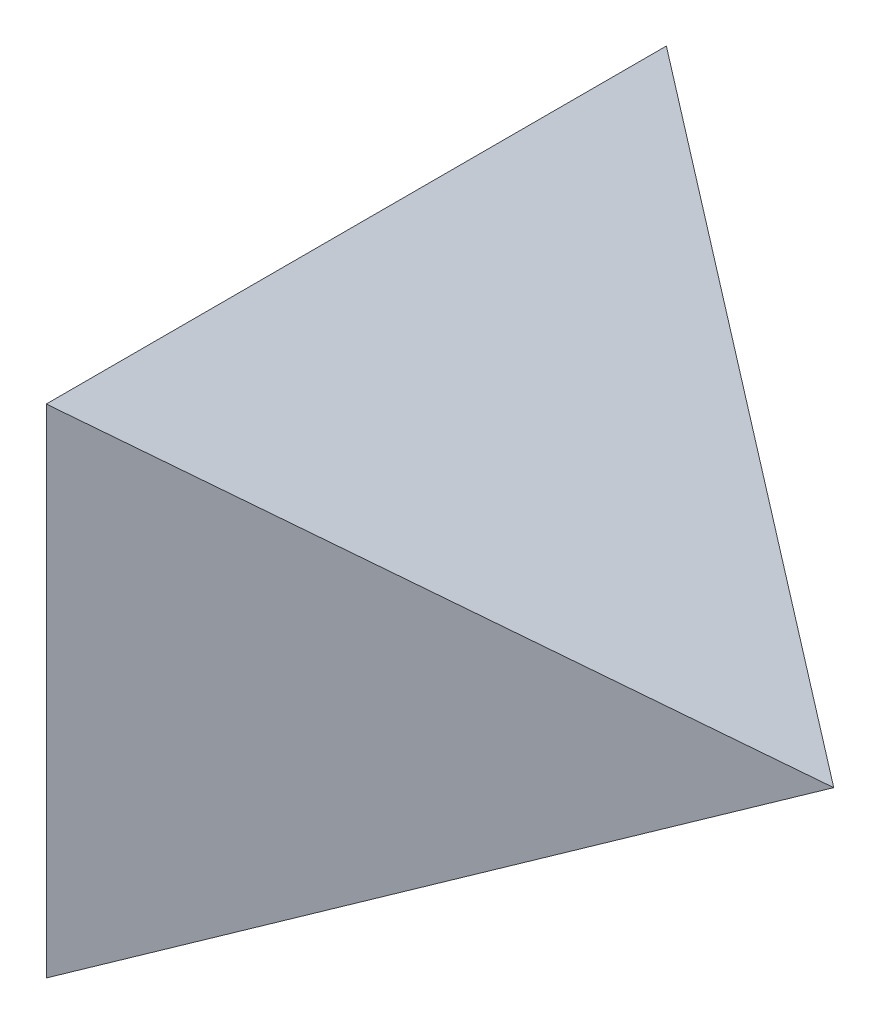
SolidWorks part; units mm, degrees
ref_plane "Front Plane" through (0, 0, 0) normal (0, 0, 1) x (1, 0, 0)
ref_plane "Top Plane" through (0, 0, 0) normal (0, 1, 0) x (1, 0, 0)
ref_plane "Right Plane" through (0, 0, 0) normal (1, 0, 0) x (0, 0, -1)
sketch "Sketch1" plane through (0, 0, 0) normal (0, 0, 1) x (1, 0, 0)
  line L0 (0, 0) -> (-3000, 1561.7012)
  line L1 (0, 0) -> (-3000, -1561.7012)
  line L2 (0, 0) -> (-3000, 0) construction
  line L3 (-3000, 1561.7012) -> (-3000, -1561.7012)
  dimension "D1" = 55
  dimension "D2" = 3000
extrude "Boss-Extrude1" add sketch "Sketch1" along normal blind 3000 and the other way blind 3000
sketch "Sketch2" plane through (0, 0, 0) normal (0, 1, 0) x (1, 0, 0)
  line L0 (0, 0) -> (-3000, 1948.2228)
  line L1 (-3000, 3000) -> (-3000, -3000) construction
  line L2 (-3000, 1948.2228) -> (-3000, -1948.2228)
  line L3 (-3000, -1948.2228) -> (0, 0)
  dimension "D1" = 66
extrude "Cut-Extrude1" cut sketch "Sketch2" against normal blind 3000 and the other way blind 3000 flip side to cut
